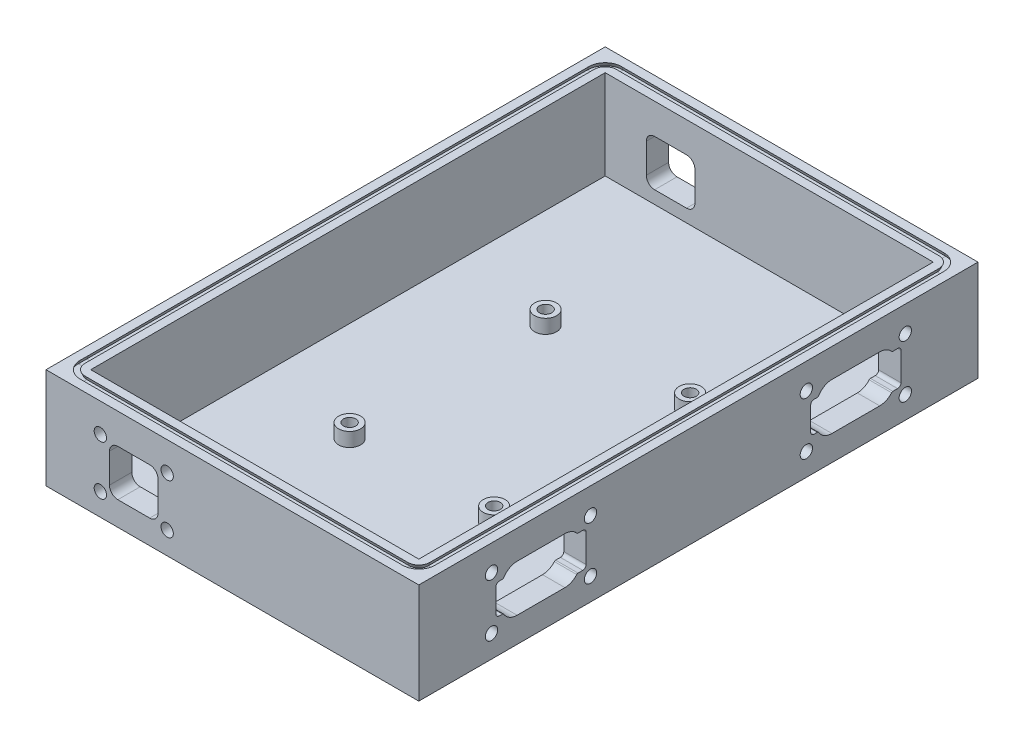
SolidWorks part; units mm, degrees
ref_plane "Front Plane" through (0, 0, 0) normal (0, 0, 1) x (1, 0, 0)
ref_plane "Top Plane" through (0, 0, 0) normal (0, 1, 0) x (1, 0, 0)
ref_plane "Right Plane" through (0, 0, 0) normal (1, 0, 0) x (0, 0, -1)
sketch "Sketch1" plane through (0, 0, 0) normal (0, 1, 0) x (1, 0, 0)
  line L1 (0, 0) -> (169.3418, 0)
  line L2 (0, 0) -> (0, 254)
  line L3 (0, 254) -> (169.3418, 254)
  line L4 (169.3418, 0) -> (169.3418, 254)
  dimension "D1" = 169.3418
  dimension "D2" = 254
extrude "Boss-Extrude1" add sketch "Sketch1" along normal blind 45.72
sketch "12 pin hole" [suppressed] plane through (254, 0, 0) normal (1, 0, 0) x (0, 0, -1)
  line L8 (50.8, 10.16) -> (95.758, 10.16) construction
  line L9 (50.8, 10.16) -> (50.8, 34.036) construction
  line L10 (50.8, 34.036) -> (95.758, 34.036) construction
  line L11 (95.758, 10.16) -> (95.758, 34.036) construction
  line L12 (55.7357, 28.956) -> (54.2925, 28.956)
  line L13 (52.7685, 27.432) -> (52.7685, 16.764)
  line L14 (54.2925, 15.24) -> (55.7357, 15.24)
  line L16 (90.087, 29.972) -> (92.2655, 29.972)
  line L17 (93.7895, 28.448) -> (93.7895, 15.748)
  line L18 (92.2655, 14.224) -> (90.087, 14.224)
  line L21 (62.4205, 25.654) -> (84.1375, 25.654) construction
  line L22 (62.4205, 25.654) -> (62.4205, 18.542) construction
  line L23 (62.4205, 18.542) -> (84.1375, 18.542) construction
  line L24 (84.1375, 25.654) -> (84.1375, 18.542) construction
  line L25 (62.4205, 32.7152) -> (84.1375, 32.7152)
  line L26 (62.4205, 11.4808) -> (84.1375, 11.4808)
  line L27 (52.7685, 22.098) -> (50.8, 22.098) construction
  line L28 (93.7895, 22.098) -> (95.758, 22.098) construction
  arc A4 (62.4205, 32.7152) -> (56.3868, 29.3222) centre (62.4205, 25.654) ccw
  arc A5 (89.5075, 30.2392) -> (84.1375, 32.7152) centre (84.1375, 25.654) ccw
  arc A6 (62.4205, 11.4808) -> (56.3868, 14.8738) centre (62.4205, 18.542) cw
  arc A7 (89.5075, 13.9568) -> (84.1375, 11.4808) centre (84.1375, 18.542) cw
  arc A8 (90.087, 29.972) -> (89.5075, 30.2392) centre (90.087, 30.734) cw
  arc A9 (90.087, 14.224) -> (89.5075, 13.9568) centre (90.087, 13.462) ccw
  arc A10 (55.7357, 15.24) -> (56.3868, 14.8738) centre (55.7357, 14.478) cw
  arc A11 (55.7357, 28.956) -> (56.3868, 29.3222) centre (55.7357, 29.718) ccw
  arc A12 (92.2655, 29.972) -> (93.7895, 28.448) centre (92.2655, 28.448) cw
  arc A13 (93.7895, 15.748) -> (92.2655, 14.224) centre (92.2655, 15.748) cw
  arc A14 (52.7685, 16.764) -> (54.2925, 15.24) centre (54.2925, 16.764) ccw
  arc A15 (54.2925, 28.956) -> (52.7685, 27.432) centre (54.2925, 27.432) ccw
  point P25 (50.8, 22.098)
  point P28 (52.7685, 22.098)
  point P29 (93.7895, 22.098)
  point P34 (62.4205, 22.098)
  point P35 (84.1375, 22.098)
  point P44 (73.279, 10.16)
  point P46 (73.279, 11.4808)
  point P59 (93.7895, 29.972)
  point P62 (93.7895, 14.224)
  point P65 (52.7685, 15.24)
  point P68 (52.7685, 28.956)
  dimension "D4" = 41.021
  dimension "D5" = 15.748
  dimension "D11" = 7.0612
  dimension "D12" = 0.762
  dimension "D13" = 1.524
  dimension "D1" = 44.958
  dimension "D2" = 23.876
  dimension "D8" = 13.716
  dimension "D9" = 21.2344
  dimension "D10" = 21.717
sketch "Sketch2" plane through (0, 45.72, 0) normal (0, 1, 0) x (1, 0, 0)
  line L0 (0, 254) -> (0, 0) construction
  line L1 (10.16, 10.16) -> (159.1818, 10.16)
  line L2 (10.16, 10.16) -> (10.16, 243.84)
  line L3 (10.16, 243.84) -> (159.1818, 243.84)
  line L4 (159.1818, 10.16) -> (159.1818, 243.84)
  line L5 (169.3418, 254) -> (0, 254) construction
  line L6 (169.3418, 0) -> (169.3418, 254) construction
  line L7 (0, 0) -> (169.3418, 0) construction
  dimension "D1" = 10.16
  dimension "D2" = 10.16
  dimension "D3" = 10.16
  dimension "D4" = 10.16
extrude "Cut-Extrude1" cut sketch "Sketch2" against normal blind 40.64
ref_plane "Plane1" through (0, 45.72, 0) normal (0, 1, 0) x (1, 0, 0)
sketch "Sketch3" plane through (0, 45.72, 0) normal (0, 1, 0) x (1, 0, 0)
  line L4 (6.35, 11.43) -> (6.35, 242.57)
  line L5 (159.1818, 243.84) -> (10.16, 243.84) construction
  line L6 (10.16, 243.84) -> (10.16, 10.16) construction
  line L7 (159.1818, 10.16) -> (159.1818, 243.84) construction
  line L8 (10.16, 10.16) -> (159.1818, 10.16) construction
  line L13 (11.43, 247.65) -> (157.9118, 247.65)
  line L14 (162.9918, 242.57) -> (162.9918, 11.43)
  line L15 (157.9118, 6.35) -> (11.43, 6.35)
  arc A0 (6.35, 242.57) -> (11.43, 247.65) centre (11.43, 242.57) cw
  arc A1 (157.9118, 247.65) -> (162.9918, 242.57) centre (157.9118, 242.57) cw
  arc A2 (162.9918, 11.43) -> (157.9118, 6.35) centre (157.9118, 11.43) cw
  arc A3 (11.43, 6.35) -> (6.35, 11.43) centre (11.43, 11.43) cw
  dimension "D5" = 5.08
  dimension "D1" = 3.81
  dimension "D2" = 3.81
  dimension "D3" = 3.81
  dimension "D4" = 3.81
ref_plane "Plane2" through (0, 0, 0) normal (0, 0, 1) x (1, 0, 0)
ref_plane "Plane3" through (0, 0, -15.24) normal (0, 0, 1) x (1, 0, 0)
sketch "Sketch4" plane through (0, 0, -15.24) normal (0, 0, 1) x (1, 0, 0)
  line L0 (4.064, 45.72) -> (3.2724, 43.942)
  line L1 (6.35, 45.72) -> (7.1416, 43.942)
  line L2 (3.2724, 43.942) -> (7.1416, 43.942)
  line L5 (4.064, 45.72) -> (6.35, 45.72)
  dimension "D1" = 1.778
  dimension "D2" = 2.286
  dimension "D3" = 66
  dimension "D4" = 66
sweep "Cut-Sweep2" cut profiles "Sketch4" path "Sketch3"
sketch "Sketch13" plane through (169.3418, 0, 0) normal (1, 0, 0) x (0, 0, -1)
  line L0 (33.02, 10.16) -> (33.02, 0) construction
  line L1 (0, 0) -> (254, 0) construction
  line L2 (33.02, 10.16) -> (0, 10.16) construction
  line L3 (0, 45.72) -> (0, 0) construction
  line L4 (220.98, 0) -> (220.98, 10.16) construction
  line L5 (220.98, 10.16) -> (254, 10.16) construction
  line L6 (254, 45.72) -> (254, 0) construction
  line B0 (33.02, 10.16) -> (77.978, 10.16) construction
  line B1 (33.02, 10.16) -> (33.02, 34.036) construction
  line B2 (33.02, 34.036) -> (77.978, 34.036) construction
  line B3 (77.978, 10.16) -> (77.978, 34.036) construction
  line B4 (37.9557, 28.956) -> (36.5125, 28.956)
  line B5 (34.9885, 27.432) -> (34.9885, 16.764)
  line B6 (36.5125, 15.24) -> (37.9557, 15.24)
  line B7 (72.307, 29.972) -> (74.4855, 29.972)
  line B8 (76.0095, 28.448) -> (76.0095, 15.748)
  line B9 (74.4855, 14.224) -> (72.307, 14.224)
  line B10 (44.6405, 32.7152) -> (66.3575, 32.7152)
  line B11 (44.6405, 11.4808) -> (66.3575, 11.4808)
  arc B12 (44.6405, 32.7152) -> (38.6068, 29.3222) centre (44.6405, 25.654) ccw
  arc B13 (71.7275, 30.2392) -> (66.3575, 32.7152) centre (66.3575, 25.654) ccw
  arc B14 (44.6405, 11.4808) -> (38.6068, 14.8738) centre (44.6405, 18.542) cw
  arc B15 (71.7275, 13.9568) -> (66.3575, 11.4808) centre (66.3575, 18.542) cw
  arc B16 (72.307, 29.972) -> (71.7275, 30.2392) centre (72.307, 30.734) cw
  arc B17 (72.307, 14.224) -> (71.7275, 13.9568) centre (72.307, 13.462) ccw
  arc B18 (37.9557, 15.24) -> (38.6068, 14.8738) centre (37.9557, 14.478) cw
  arc B19 (37.9557, 28.956) -> (38.6068, 29.3222) centre (37.9557, 29.718) ccw
  arc B20 (74.4855, 29.972) -> (76.0095, 28.448) centre (74.4855, 28.448) cw
  arc B21 (76.0095, 15.748) -> (74.4855, 14.224) centre (74.4855, 15.748) cw
  arc B22 (34.9885, 16.764) -> (36.5125, 15.24) centre (36.5125, 16.764) ccw
  arc B23 (36.5125, 28.956) -> (34.9885, 27.432) centre (36.5125, 27.432) ccw
  line B24 (176.022, 10.16) -> (220.98, 10.16) construction
  line B25 (176.022, 10.16) -> (176.022, 34.036) construction
  line B26 (176.022, 34.036) -> (220.98, 34.036) construction
  line B27 (220.98, 10.16) -> (220.98, 34.036) construction
  line B28 (180.9577, 28.956) -> (179.5145, 28.956)
  line B29 (177.9905, 27.432) -> (177.9905, 16.764)
  line B30 (179.5145, 15.24) -> (180.9577, 15.24)
  line B31 (215.309, 29.972) -> (217.4875, 29.972)
  line B32 (219.0115, 28.448) -> (219.0115, 15.748)
  line B33 (217.4875, 14.224) -> (215.309, 14.224)
  line B34 (187.6425, 32.7152) -> (209.3595, 32.7152)
  line B35 (187.6425, 11.4808) -> (209.3595, 11.4808)
  arc B36 (187.6425, 32.7152) -> (181.6088, 29.3222) centre (187.6425, 25.654) ccw
  arc B37 (214.7295, 30.2392) -> (209.3595, 32.7152) centre (209.3595, 25.654) ccw
  arc B38 (187.6425, 11.4808) -> (181.6088, 14.8738) centre (187.6425, 18.542) cw
  arc B39 (214.7295, 13.9568) -> (209.3595, 11.4808) centre (209.3595, 18.542) cw
  arc B40 (215.309, 29.972) -> (214.7295, 30.2392) centre (215.309, 30.734) cw
  arc B41 (215.309, 14.224) -> (214.7295, 13.9568) centre (215.309, 13.462) ccw
  arc B42 (180.9577, 15.24) -> (181.6088, 14.8738) centre (180.9577, 14.478) cw
  arc B43 (180.9577, 28.956) -> (181.6088, 29.3222) centre (180.9577, 29.718) ccw
  arc B44 (217.4875, 29.972) -> (219.0115, 28.448) centre (217.4875, 28.448) cw
  arc B45 (219.0115, 15.748) -> (217.4875, 14.224) centre (217.4875, 15.748) cw
  arc B46 (177.9905, 16.764) -> (179.5145, 15.24) centre (179.5145, 16.764) ccw
  arc B47 (179.5145, 28.956) -> (177.9905, 27.432) centre (179.5145, 27.432) ccw
  dimension "D1" = 33.02
  dimension "D2" = 10.16
sketch_block_instance "Block7-3"
sketch_block "Block7" parameters "D6"=7.0612, "D7"=0.762, "D8"=1.524, "D1"=44.958, "D2"=23.876, "D3"=41.021, "D4"=21.2344, "D5"=21.717
sketch_block_instance "Block7-4"
extrude "Cut-Extrude10" cut sketch "Sketch13" against normal up to next
sketch "12 pin mount" plane through (169.3418, 0, 0) normal (1, 0, 0) x (0, 0, -1)
  circle A0 centre (77.978, 34.036) radius 2.8
  circle A1 centre (77.978, 10.16) radius 2.8
  circle A2 centre (33.02, 10.16) radius 2.8
  circle A3 centre (33.02, 34.036) radius 2.8
  circle A4 centre (176.022, 34.036) radius 2.8
  circle A5 centre (220.98, 34.036) radius 2.8
  circle A6 centre (220.98, 10.16) radius 2.8
  circle A7 centre (176.022, 10.16) radius 2.8
  dimension "D1" = 5.6
extrude "Cut-Extrude3" cut sketch "12 pin mount" against normal blind 5.5
sketch "4 pin connector" plane through (0, 0, 0) normal (0, 0, 1) x (1, 0, 0)
  line L0 (55.0418, 0) -> (55.0418, 10.16) construction
  line L1 (0, 0) -> (169.3418, 0) construction
  line L2 (55.0418, 10.16) -> (169.3418, 10.16) construction
  line L3 (169.3418, 45.72) -> (169.3418, 0) construction
  line L5 (24.6888, 32.6136) -> (55.0418, 32.6136) construction
  line L6 (24.6888, 32.6136) -> (24.6888, 10.16) construction
  line L7 (24.6888, 10.16) -> (55.0418, 10.16) construction
  line L8 (55.0418, 32.6136) -> (55.0418, 10.16) construction
  line L9 (32.6263, 31.877) -> (47.1043, 31.877)
  line L10 (28.8163, 28.067) -> (28.8163, 14.7066)
  line L11 (32.6263, 10.8966) -> (47.1043, 10.8966)
  line L12 (50.9143, 28.067) -> (50.9143, 14.7066)
  line L13 (39.8653, 10.8966) -> (39.8653, 31.877) construction
  line L14 (28.8163, 21.3868) -> (50.9143, 21.3868) construction
  arc A0 (47.1043, 31.877) -> (50.9143, 28.067) centre (47.1043, 28.067) cw
  arc A1 (47.1043, 10.8966) -> (50.9143, 14.7066) centre (47.1043, 14.7066) ccw
  arc A2 (28.8163, 14.7066) -> (32.6263, 10.8966) centre (32.6263, 14.7066) ccw
  arc A3 (32.6263, 31.877) -> (28.8163, 28.067) centre (32.6263, 28.067) ccw
  point P4 (39.8653, 21.3868)
  point P12 (39.8653, 10.16)
  point P15 (55.0418, 21.3868)
  point P20 (50.9143, 31.877)
  point P24 (50.9143, 10.8966)
  point P29 (28.8163, 31.877)
  dimension "D1" = 22.098
  dimension "D7" = 3.81
  dimension "D2" = 22.4536
  dimension "D3" = 30.353
  dimension "D4" = 10.16
  dimension "D5" = 114.3
  dimension "D6" = 20.9804
extrude "Cut-Extrude5" cut sketch "4 pin connector" against normal up to next
extrude "Cut-Extrude6" cut sketch "Sketch5<2>" along normal up to next from surface starting at face at (84.6709, 22.86, -254)
sketch "Sketch5<2>" plane through (0, 0, 0) normal (0, 0, 1) x (1, 0, 0) same geometry as "4 pin connector"
sketch "Sketch6" plane through (0, 0, 0) normal (0, 0, 1) x (1, 0, 0)
  circle A0 centre (55.0418, 32.6136) radius 2.8
  circle A1 centre (55.0418, 10.16) radius 2.8
  circle A2 centre (24.6888, 10.16) radius 2.8
  circle A3 centre (24.6888, 32.6136) radius 2.8
  dimension "D1" = 5.6
extrude "Cut-Extrude7" cut sketch "Sketch6" against normal blind 5.5
extrude "Cut-Extrude8" cut sketch "Sketch6<2>" along normal blind 5.5 from surface starting at face at (39.8653, 21.3868, -254)
sketch "Sketch6<2>" plane through (0, 0, 0) normal (0, 0, 1) x (1, 0, 0) same geometry as "Sketch6"
sketch "Sketch7" plane through (0, 5.08, 0) normal (0, 1, 0) x (1, 0, 0)
  line L0 (121.0818, 127) -> (159.1818, 127) construction
  line L1 (159.1818, 10.16) -> (159.1818, 243.84) construction
  line L2 (159.1818, 10.16) -> (159.1818, 243.84) construction
  line L5 (121.0818, 82.485) -> (55.4218, 82.485) construction
  line L6 (121.0818, 82.485) -> (121.0818, 171.515) construction
  line L7 (121.0818, 171.515) -> (55.4218, 171.515) construction
  line L8 (55.4218, 82.485) -> (55.4218, 171.515) construction
  circle A0 centre (55.4218, 82.485) radius 5
  circle A1 centre (121.0818, 82.485) radius 5
  circle A2 centre (121.0818, 171.515) radius 5
  circle A3 centre (55.4218, 171.515) radius 5
  point P6 (142.24, 114.3)
  dimension "D1" = 10
  dimension "D2" = 89.03
  dimension "D3" = 65.66
  dimension "D4" = 38.1
sketch "Sketch8" plane through (0, 5.08, 0) normal (0, 1, 0) x (1, 0, 0)
  circle A0 centre (55.4218, 171.515) radius 2.8
  circle A1 centre (121.0818, 171.515) radius 2.8
  circle A2 centre (121.0818, 82.485) radius 2.8
  circle A3 centre (55.4218, 82.485) radius 2.8
  dimension "D1" = 5.6
extrude "Boss-Extrude2" add sketch "Sketch7" along normal blind 6.35
extrude "Cut-Extrude9" cut sketch "Sketch8" against normal blind 5.5 from surface starting at face at (121.0818, 11.43, -77.485)
equation "\"M4 insert  width\"= 5.6mm"
equation "\"M4 insert  depth\"= 5.5mm"
equation "\"depth\"=0.1"
